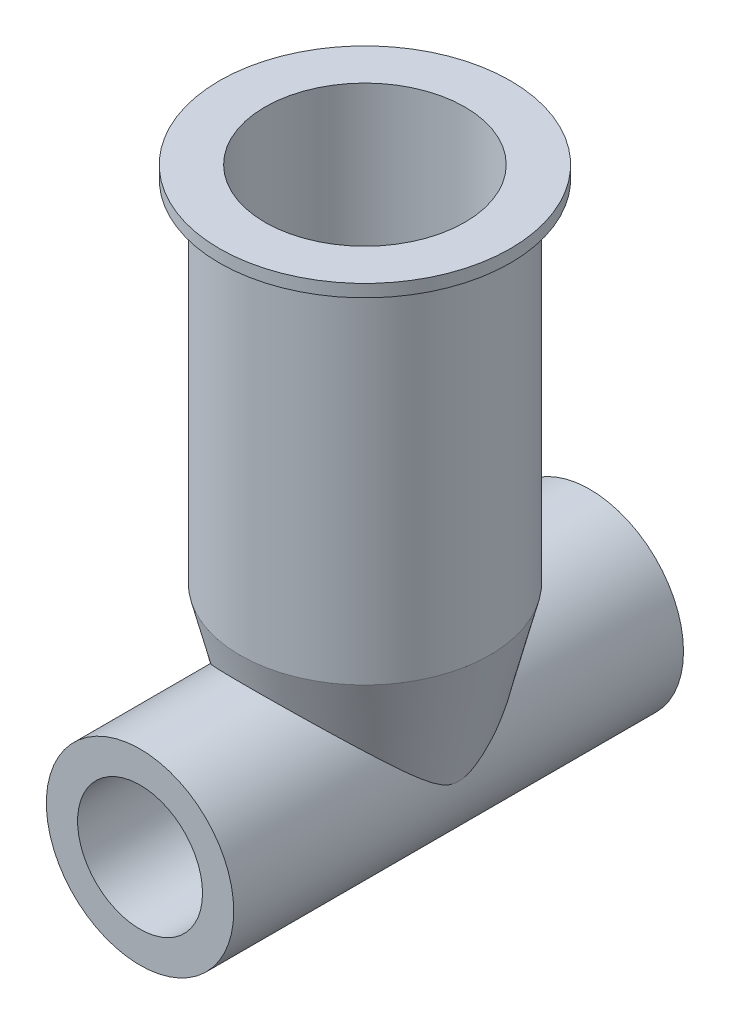
SolidWorks part; units mm, degrees
ref_plane "Front Plane" through (0, 0, 0) normal (0, 0, 1) x (1, 0, 0)
ref_plane "Top Plane" through (0, 0, 0) normal (0, 1, 0) x (1, 0, 0)
ref_plane "Right Plane" through (0, 0, 0) normal (1, 0, 0) x (0, 0, -1)
sketch "Sketch1" plane through (0, 0, 0) normal (0, 0, 1) x (1, 0, 0)
  circle A0 centre (0, 0) radius 7.5
  circle A1 centre (0, 0) radius 5
  dimension "D1" = 15
  dimension "D2" = 10
extrude "Boss-Extrude1" add sketch "Sketch1" along normal blind 18 and the other way blind 18
ref_plane "Plane1" through (0, 10, 0) normal (0, 1, 0) x (1, 0, 0)
sketch "Sketch3" plane through (0, 10, 0) normal (0, 1, 0) x (1, 0, 0)
  circle A0 centre (0, 0) radius 10
  dimension "D1" = 20
sketch "Sketch2" plane through (0, 0, 0) normal (0, 1, 0) x (1, 0, 0)
  circle A0 centre (0, 0) radius 7.5
loft "Loft1" add profiles "Sketch3", "Sketch2" connector at (0, 10, 10) connector at (0, 0, 7.5)
sketch "Sketch4" plane through (0, 10, 0) normal (0, 1, 0) x (1, 0, 0)
  circle A0 centre (0, 0) radius 10
  circle A1 centre (0, 0) radius 8
  dimension "D1" = 16
extrude "Boss-Extrude3" add sketch "Sketch4" along normal blind 28
sketch "Sketch5" plane through (0, 38, 0) normal (0, 1, 0) x (1, 0, 0)
  circle A0 centre (0, 0) radius 8
  circle A1 centre (0, 0) radius 11.6436
extrude "Boss-Extrude4" add sketch "Sketch5" along normal blind 1
